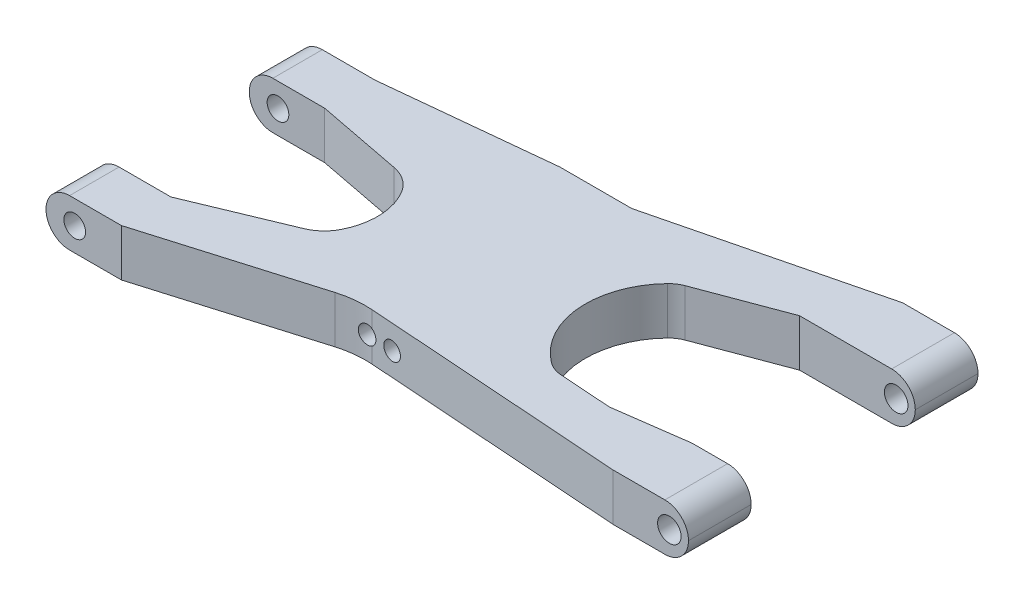
SolidWorks part; units mm, degrees
ref_plane "Front Plane" through (0, 0, 0) normal (0, 0, 1) x (1, 0, 0)
ref_plane "Top Plane" through (0, 0, 0) normal (0, 1, 0) x (1, 0, 0)
ref_plane "Right Plane" through (0, 0, 0) normal (1, 0, 0) x (0, 0, -1)
sketch "Sketch1" plane through (0, 0, 0) normal (0, 1, 0) x (1, 0, 0)
  line L0 (0, 0) -> (0, 38.989)
  line L1 (-81.915, 29.4386) -> (-71.628, 29.4386)
  line L2 (-81.915, 29.4386) -> (-81.915, -4.5974)
  line L3 (0, 0) -> (-10.16, 0)
  line L4 (-71.628, 29.4386) -> (-10.16, 38.989)
  line L5 (0, 38.989) -> (-10.16, 38.989)
  line L6 (-71.755, -4.5974) -> (-10.16, 0)
  line L8 (-81.915, -4.5974) -> (-71.755, -4.5974)
  dimension "D1" = 38.989
  dimension "D2" = 34.036
  dimension "D3" = 81.915
  dimension "D4" = 9.5504
  dimension "D5" = 4.5974
  dimension "D6" = 61.468
  dimension "D7" = 10.16
  dimension "D8" = 10.16
  dimension "D9" = 10.16
  dimension "D10" = 61.595
extrude "Boss-Extrude1" add sketch "Sketch1" along normal blind 6.35
fillet "Fillet2" radius 3.175 4 edges at (0, 0, -19.4945) (0, 6.35, -19.4945) (-81.915, 0, -12.4206) (-81.915, 6.35, -12.4206)
sketch "Sketch2" plane through (-0.605, 0, 0) normal (0, 0, -1) x (-1, 0, 0)
  circle A0 centre (1.9663, 3.175) radius 1.5875
  circle A1 centre (77.4406, 3.175) radius 1.4605
  dimension "D1" = 2.921
  dimension "D2" = 3.175
extrude "Cut-Extrude2" cut sketch "Sketch2" along normal through all and the other way through all
sketch "Sketch3" plane through (0, 0, 0) normal (0, 1, 0) x (1, 0, 0)
  line L0 (-81.915, 22.7711) -> (-71.755, 22.7711)
  line L1 (0, 30.5435) -> (0, 8.4455)
  line L2 (-10.668, 19.4945) -> (-35.4657, 19.4945) construction
  line L3 (-81.915, 22.7711) -> (-81.915, 2.0701)
  line L4 (-71.755, 2.0701) -> (-81.915, 2.0701)
  line L5 (-71.755, 22.7711) -> (-58.4876, 20.2076)
  line L6 (-71.114, 12.4206) -> (-37.8214, 12.4206) construction
  line L7 (0, 30.5435) -> (-7.9756, 30.5435)
  line L8 (-7.9756, 8.4455) -> (-17.7396, 7.0963)
  line L9 (-7.9756, 8.4455) -> (0, 8.4455)
  line L10 (-71.755, 2.0701) -> (-57.7774, 7.8837)
  line L13 (-17.7396, 7.0963) -> (-24.7644, 7.5875)
  line L14 (-15.5852, 30.5435) -> (-26.7956, 26.3446)
  line L15 (-7.9756, 30.5435) -> (-15.5852, 30.5435)
  arc A0 (-58.4876, 20.2076) -> (-57.7774, 7.8837) centre (-64.2945, 13.6906) cw
  arc A1 (-26.7699, 8.3292) -> (-28.2109, 25.4119) centre (-19.956, 17.5061) cw
  arc A2 (-24.7644, 7.5875) -> (-26.7699, 8.3292) centre (-24.4986, 11.3882) cw
  arc A3 (-26.7956, 26.3446) -> (-28.2109, 25.4119) centre (-25.4593, 22.7767) ccw
  point P18 (-25.7556, 7.6568)
  point P27 (-27.524, 26.0718)
  dimension "D9" = 12.3444
  dimension "D10" = 13.5128
  dimension "D19" = 3.81
  dimension "D20" = 11.43
  dimension "D1" = 20.701
  dimension "D3" = 6.6675
  dimension "D4" = 10.16
  dimension "D5" = 22.098
  dimension "D6" = 8.4455
  dimension "D7" = 8.4455
  dimension "D8" = 7.9756
  dimension "D11" = 18.415
  dimension "D16" = 15.1384
  dimension "D21" = 6.6675
extrude "Cut-Extrude5" cut sketch "Sketch3" along normal through all
sketch "Sketch5" plane through (0, 6.35, 0) normal (0, 1, 0) x (1, 0, 0)
  line L0 (-10.16, 38.989) -> (-53.7874, 28.1798)
  line L1 (-53.7874, 28.1798) -> (-71.628, 29.4386)
  line L2 (-71.628, 29.4386) -> (-10.16, 38.989)
  line L3 (-10.16, 0) -> (-47.3941, 2.6271)
  line L4 (-47.3941, 2.6271) -> (-71.755, -4.5974)
  line L5 (-71.755, -4.5974) -> (-10.16, 0)
extrude "Cut-Extrude7" cut sketch "Sketch5" against normal blind 25.4
ref_plane "Plane1" through (0, 0, -31.75) normal (0, 0, 1) x (1, 0, 0)
sketch "Sketch6" plane through (0, 0, -31.75) normal (0, 0, 1) x (1, 0, 0)
  line L0 (-45.72, 3.1087) -> (-42.164, 3.1087) construction
  line L3 (-38.5716, 6.35) -> (-38.5716, 0)
  line L4 (-10.16, 6.35) -> (-10.16, 0) construction
  line L5 (-53.7874, 6.35) -> (-10.16, 6.35) construction
  line L6 (-53.7874, 0) -> (-10.16, 0) construction
  line L7 (-38.5716, 0) -> (-49.0502, 0)
  line L8 (-49.0502, 0) -> (-49.0502, 6.35)
  line L9 (-49.0502, 6.35) -> (-38.5716, 6.35)
  circle A2 centre (-45.72, 3.1087) radius 1.2065
  circle A3 centre (-42.164, 3.1087) radius 1.2065
  point P2 (-43.942, 3.1087)
  point P11 (-10.16, 3.175)
  dimension "D3" = 2.413
  dimension "D4" = 32.004
extrude "Boss-Extrude2" add sketch "Sketch6" along normal blind 12.7
fillet "Fillet5" radius 12.7 2 edges at (-53.7874, 3.175, -28.1798) (-47.3941, 3.175, -2.6271)
fillet "Fillet6" radius 5.08 2 edges at (-57.7774, 3.175, -7.8837) (-58.4876, 3.175, -20.2076)
sketch "Sketch9" plane through (0, 6.35, 0) normal (0, 1, 0) x (1, 0, 0)
  line L0 (-49.0502, 31.75) -> (-71.628, 29.4386)
  line L1 (-71.628, 29.4386) -> (-71.628, 26.6974)
  line L2 (-71.628, 26.6974) -> (-49.0502, 26.6974)
  line L3 (-49.0502, 26.6974) -> (-49.0502, 31.75)
extrude "Boss-Extrude3" add sketch "Sketch9" against normal up to surface (6.35 mm away) up to face at (-42.4229, 0, -16.8721)
sketch "Sketch10" plane through (0, 0, -31.75) normal (0, 0, -1) x (-1, 0, 0)
  circle A0 centre (42.164, 3.1087) radius 1.2065
  circle A1 centre (45.72, 3.1087) radius 1.2065
extrude "Cut-Extrude9" cut sketch "Sketch10" against normal through all
